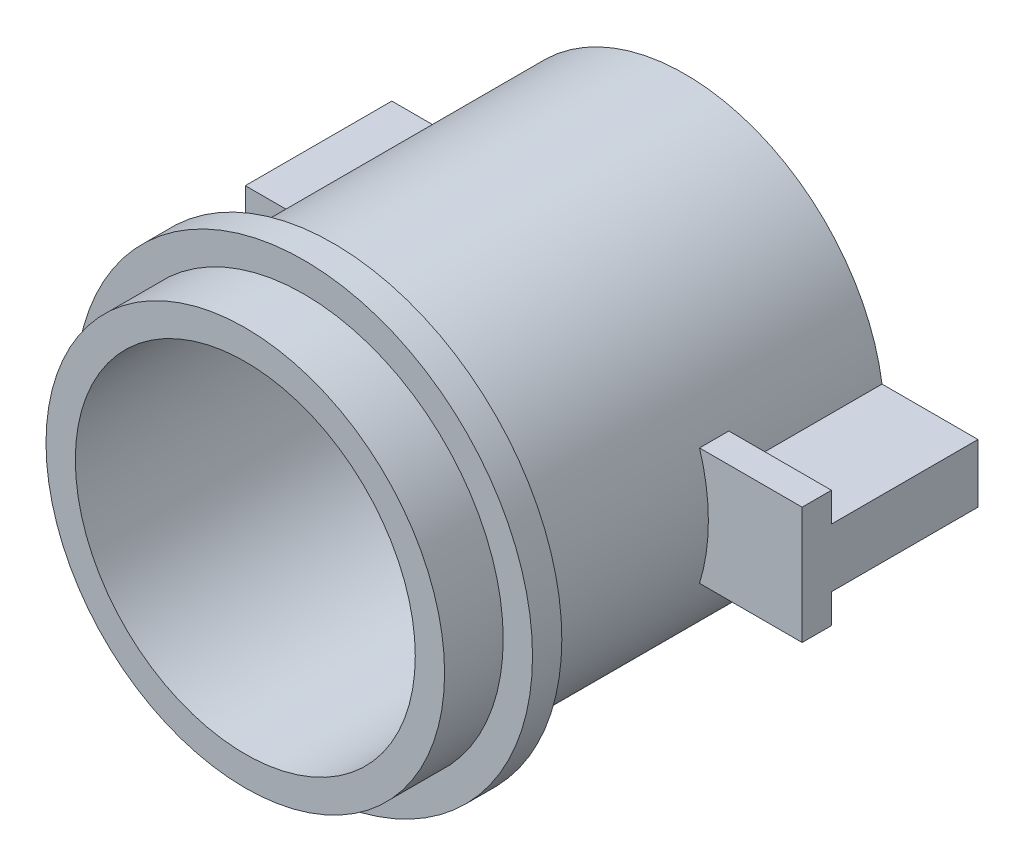
SolidWorks part; units mm, degrees
ref_plane "Plan de face" through (0, 0, 0) normal (0, 0, 1) x (1, 0, 0)
ref_plane "Plan de dessus" through (0, 0, 0) normal (0, 1, 0) x (1, 0, 0)
ref_plane "Plan de droite" through (0, 0, 0) normal (1, 0, 0) x (0, 0, -1)
sketch "Esquisse1" plane through (0, 0, 0) normal (0, 0, 1) x (1, 0, 0)
  circle A0 centre (0, 0) radius 6.8
extrude "Boss.-Extru.1" add sketch "Esquisse1" along normal blind 15
shell "Coque1" thickness 1 removed face at (6.8, 0, 15)
sketch "Esquisse2" plane through (0, 0, 0) normal (0, 0, -1) x (-1, 0, 0)
  circle A0 centre (0, 0) radius 3.55
extrude "Enlèv. mat.-Extru.1" cut sketch "Esquisse2" against normal blind 15
chamfer "Chanfrein1" distance 3 angle 45 1 edges at (5.8, 0, 1)
sketch "Esquisse3" plane through (0, 0, 0) normal (0, 0, -1) x (-1, 0, 0)
  line L0 (0, 0) -> (-13.3501, 0) construction
  line L1 (-6.7261, 1) -> (-10, 1)
  line L2 (10, -1) -> (6.7261, -1)
  line L3 (10, -1) -> (10, 1)
  line L4 (10, 1) -> (6.7261, 1)
  line L5 (-10, -1) -> (-10, 1)
  line L6 (10, -1) -> (-10, 1) construction
  line L7 (10, 1) -> (-10, -1) construction
  line L8 (-6.7261, -1) -> (-10, -1)
  arc A0 (6.7261, -1) -> (6.7261, 1) centre (0, 0) ccw
  arc A1 (-6.7261, 1) -> (-6.7261, -1) centre (0, 0) ccw
  dimension "D1" = 20
  dimension "D2" = 2
extrude "Boss.-Extru.2" add sketch "Esquisse3" against normal blind 5
sketch "Esquisse4" plane through (0, 0, 5) normal (0, 0, 1) x (1, 0, 0)
  line L0 (10, 2) -> (10, -2)
  line L1 (6.4992, 2) -> (5.4443, 2)
  line L2 (6.4992, -2) -> (5.4443, -2)
  line L9 (11, -2) -> (11, 2)
  line L10 (11, 2) -> (5.4443, 2)
  line L11 (5.4443, -2) -> (11, -2)
  line L13 (10, 2) -> (6.4992, 2)
  line L14 (6.4992, -2) -> (10, -2)
  circle A1 centre (0, 0) radius 6.8 construction
  arc A3 (5.4443, -2) -> (5.4443, 2) centre (0, 0) ccw
  arc A4 (5.4443, 2) -> (5.4443, -2) centre (0, 0) cw
  dimension "D1" = 1
extrude "Boss.-Extru.3" add sketch "Esquisse4" along normal blind 1
sketch "Esquisse5" plane through (0, 0, 15) normal (0, 0, 1) x (1, 0, 0)
  circle A0 centre (0, 0) radius 6.8
  circle A1 centre (0, 0) radius 7.8
extrude "Boss.-Extru.4" add sketch "Esquisse5" against normal blind 1 from offset 2 offset against normal yes
